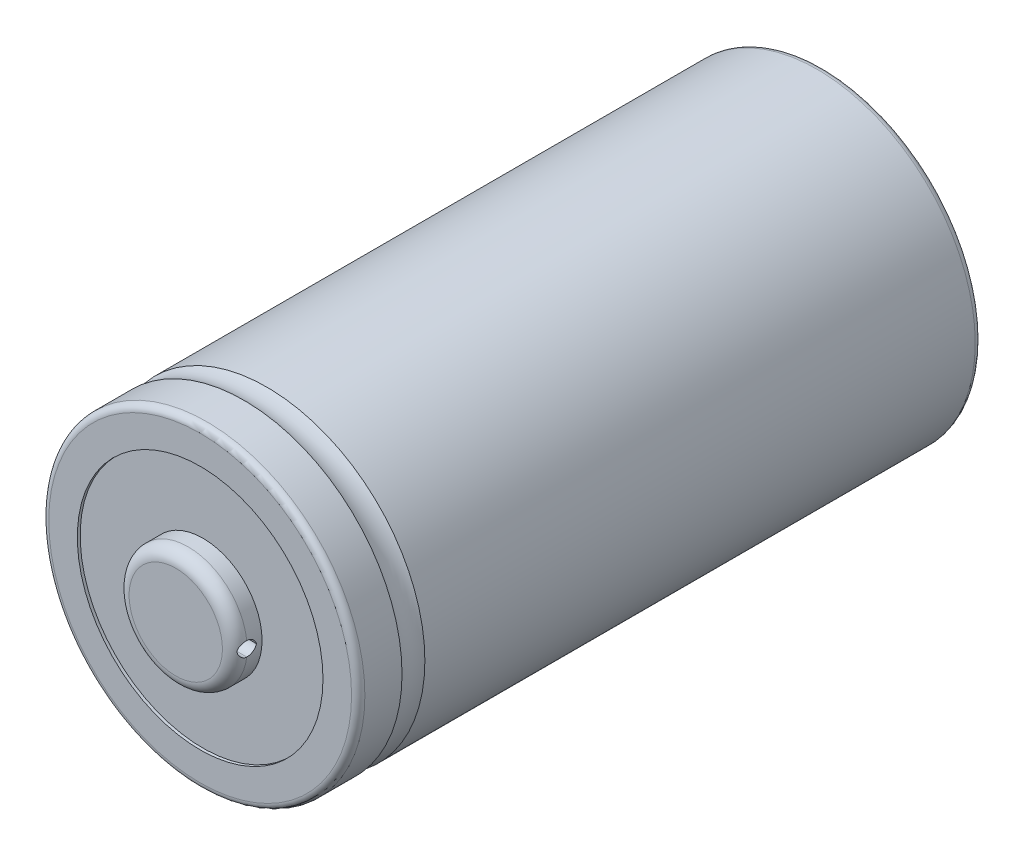
SolidWorks part; units mm, degrees
ref_plane "Front Plane" through (0, 0, 0) normal (0, 0, 1) x (1, 0, 0)
ref_plane "Top Plane" through (0, 0, 0) normal (0, 1, 0) x (1, 0, 0)
ref_plane "Right Plane" through (0, 0, 0) normal (1, 0, 0) x (0, 0, -1)
sketch "Sketch1" plane through (0, 0, 0) normal (0, 0, 1) x (1, 0, 0)
  circle A0 centre (0, 0) radius 8.3
  dimension "D1" = 16.6
extrude "Boss-Extrude1" add sketch "Sketch1" along normal blind 32.75
sketch "Sketch2" plane through (0, 0, 0) normal (0, 0, -1) x (-1, 0, 0)
  circle A0 centre (0, 0) radius 6.45
  circle A1 centre (0, 0) radius 8.3 construction
  dimension "D1" = 1.85
extrude "Cut-Extrude1" cut sketch "Sketch2" against normal blind 0.15
sketch "Sketch3" plane through (0, 0, 32.75) normal (0, 0, 1) x (1, 0, 0)
  circle A0 centre (0, 0) radius 6.45
  circle A1 centre (0, 0) radius 8.3 construction
  dimension "D1" = 1.85
extrude "Cut-Extrude2" cut sketch "Sketch3" against normal blind 0.15
fillet "Fillet1" radius 0.35 2 edges at (8.3, 0, 0) (8.3, 0, 32.75)
sketch "Sketch4" plane through (0, 0, 0) normal (0, 1, 0) x (1, 0, 0)
  line L0 (-7.95, -32.75) -> (7.95, -32.75) construction
  line L1 (8.3, -32.4) -> (8.3, -0.35) construction
  circle A0 centre (9.6775, -29.85) radius 1.5025
  point P4 (8.3, -30.45)
  point P6 (8.175, -29.85)
  point P7 (8.3, -29.25)
  dimension "D1" = 2.9
  dimension "D2" = 8.175
  dimension "D3" = 1.2
ref_plane "Plane1" through (0, 0, 29.85) normal (0, 0, 1) x (1, 0, 0)
sketch "Sketch5" plane through (0, 0, 29.85) normal (0, 0, 1) x (1, 0, 0)
  circle A0 centre (0, 0) radius 9.6775
sweep "Cut-Sweep1" cut profiles "Sketch4" path "Sketch5"
sketch "Sketch6" plane through (0, 0, 32.6) normal (0, 0, 1) x (1, 0, 0)
  circle A0 centre (0, 0) radius 3.1
  dimension "D1" = 6.2
extrude "Boss-Extrude2" add sketch "Sketch6" along normal offset from surface (1.43 mm away) 1.28 separate body up to face at (7.95, 0, 32.75) offset beyond the face yes
fillet "Fillet2" radius 0.65 1 edges at (3.1, 0, 34.03)
sketch "Sketch8" plane through (0, 0, 0) normal (1, 0, 0) x (0, 0, -1)
  line L1 (-33.78, 0.375) -> (-32.88, 0.375)
  line L2 (-33.78, 0.375) -> (-33.78, -0.375)
  line L3 (-33.78, -0.375) -> (-32.88, -0.375)
  line L4 (-32.88, 0.375) -> (-32.88, -0.375)
  line L5 (-33.78, 0.375) -> (-32.88, -0.375) construction
  line L6 (-33.78, -0.375) -> (-32.88, 0.375) construction
  line L7 (-34.03, 2.45) -> (-34.03, -2.45) construction
  point P4 (-33.33, 0)
  point P7 (0, 0)
  dimension "D1" = 0.75
  dimension "D2" = 0.9
  dimension "D3" = 0.25
extrude "Cut-Extrude3" cut sketch "Sketch8" against normal through all both and the other way through all
fillet "Fillet3" radius 0.4 2 edges at (0, -0.375, 33.78) (0, 0.375, 33.78)
fillet "Fillet4" radius 0.5 2 edges at (0, 0.375, 32.88) (0, -0.375, 32.88)
equation "\"D1@Sketch3\"=\"D1@Sketch2\""
equation "\"D2@Sketch4\"=16.35/2"
